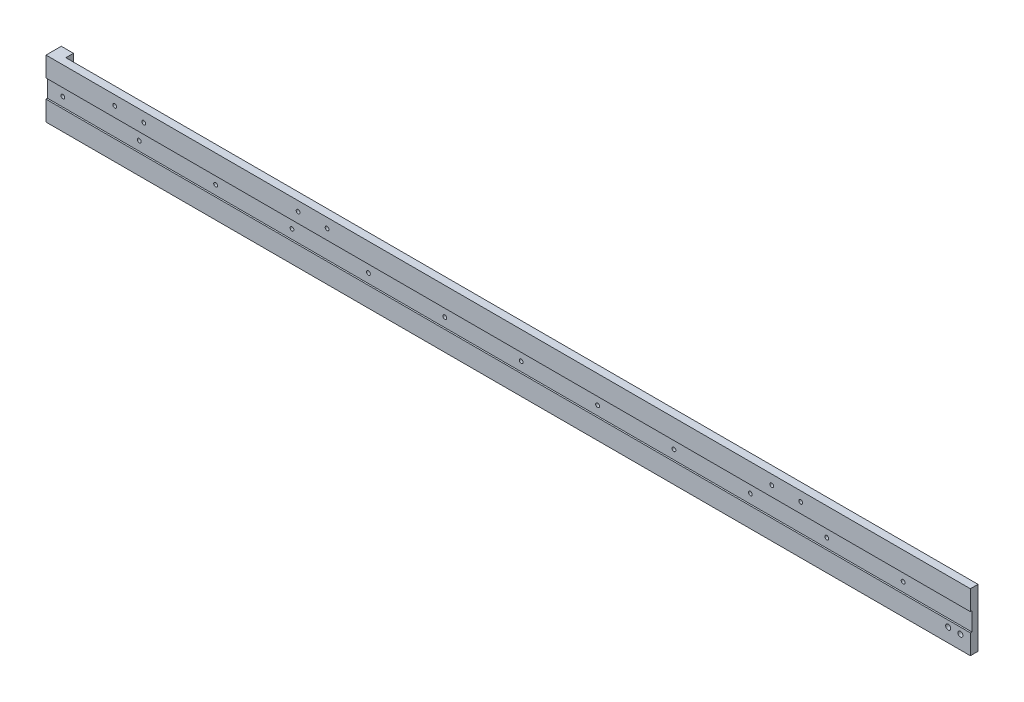
SolidWorks part; units mm, degrees
ref_plane "前视基准面" through (0, 0, 0) normal (0, 0, 1) x (1, 0, 0)
ref_plane "上视基准面" through (0, 0, 0) normal (0, 1, 0) x (1, 0, 0)
ref_plane "右视基准面" through (0, 0, 0) normal (1, 0, 0) x (0, 0, -1)
sketch "草图1" plane through (0, 0, 0) normal (0, 0, 1) x (1, 0, 0)
  line L1 (0, 0) -> (595, 0)
  line L2 (0, 0) -> (0, 38)
  line L3 (0, 38) -> (595, 38)
  line L4 (595, 0) -> (595, 38)
  dimension "D1" = 38
  dimension "D2" = 595
extrude "凸台-拉伸1" add sketch "草图1" along normal blind 5
hole_wizard "M3 螺纹孔1" positions "草图2" profile "草图3" tap size "M3" standard "ISO" end condition through all
sketch "草图2" plane through (0, 0, 5) normal (0, 0, 1) x (1, 0, 0)
  line L0 (0, 19) -> (40.9231, 19) construction
  line L1 (0, 38) -> (0, 0) construction
  point P0 (10, 19)
  dimension "D1" = 10
sketch "草图3" plane through (10, 19, 5) normal (1, 0, 0) x (0, -1, 0)
  line L0 (0, 0) -> (0, 5)
  line L1 (0, 5) -> (1.25, 5)
  line L2 (1.25, 5) -> (1.25, 0)
  line L5 (1.25, 0) -> (0, 0)
  line L11 (0, -6.35) -> (0, 107.95) construction
  dimension "通孔螺纹孔钻头直径" = 2.5
  dimension "通孔螺纹孔钻头深度" = 5
cosmetic thread "孔螺蚊线1" parameters "D2"=3
pattern_linear "阵列(线性)1" count 12 spacing 50 along (1, 0, 0) of "M3 螺纹孔1"
sketch "草图4" plane through (0, 0, 5) normal (0, 0, 1) x (1, 0, 0)
  line L0 (0, 19) -> (90.1433, 19) construction
  line L1 (0, 38) -> (0, 0) construction
  line L2 (595, 0) -> (595, 38) construction
  line L3 (0, 25) -> (595, 25)
  line L4 (0, 25) -> (0, 13)
  line L5 (0, 13) -> (595, 13)
  line L6 (595, 25) -> (595, 13)
  dimension "D1" = 12
extrude "切除-拉伸1" cut sketch "草图4" against normal blind 1
sketch "草图5" plane through (0, 0, 0) normal (-1, 0, 0) x (0, 0, 1)
  line L1 (0, 38) -> (-5, 38)
  line L2 (0, 38) -> (0, 0)
  line L3 (0, 0) -> (-5, 0)
  line L4 (-5, 38) -> (-5, 0)
  dimension "D1" = 5
extrude "凸台-拉伸2" add sketch "草图5" against normal blind 8
hole_wizard "M4 螺纹孔1" positions "草图6" profile "草图7" tap size "M4" standard "ISO"
sketch "草图6" plane through (0, 0, 0) normal (-1, 0, 0) x (0, 0, 1)
  point P0 (0.6955, 14)
  point P3 (0.6955, 4)
sketch "草图7" plane through (0, 14, 0.6955) normal (0, 1, 0) x (0, 0, 1)
  line L0 (0, 0) -> (0, 6.9914)
  line L1 (0, 6.9914) -> (1.65, 6)
  line L2 (1.65, 6) -> (1.65, 0)
  line L5 (1.65, 0) -> (0, 0)
  line L10 (0, 6.9914) -> (-1.65, 6) construction
  line L11 (0, -6.35) -> (0, 107.95) construction
  dimension "螺纹孔钻头直径" = 3.3
  dimension "螺纹孔钻头深度" = 6
  dimension "导头角度" = 118
cosmetic thread "孔螺蚊线2" parameters "D1"=6, "D2"=4
cosmetic thread "孔螺蚊线3" parameters "D1"=6, "D2"=4
sketch "草图8" plane through (595, 0, 0) normal (1, 0, 0) x (0, 0, -1)
  line L0 (-5, 0) -> (-5, 13)
  line L1 (-5, 13) -> (-4, 13)
  line L2 (-4, 13) -> (-4, 25)
  line L3 (-4, 25) -> (-5, 25)
  line L4 (-5, 25) -> (-5, 38)
  line L5 (-5, 38) -> (0, 38)
  line L6 (0, 38) -> (0, 0)
  line L7 (0, 0) -> (-5, 0)
extrude "凸台-拉伸3" add sketch "草图8" along normal blind 10
hole_wizard "M4 螺纹孔2" positions "草图9" profile "草图10" tap size "M4" standard "ISO"
sketch "草图9" plane through (0, 0, 5) normal (0, 0, 1) x (1, 0, 0)
  line L0 (0, 0) -> (605, 0) construction
  line L1 (605, 13) -> (605, 0) construction
  point P3 (598.5, 9.0024)
  point P10 (590.5, 9.0024)
  dimension "D1" = 9.0024
  dimension "D2" = 6.5
  dimension "D3" = 8
sketch "草图10" plane through (598.5, 9.0024, 5) normal (1, 0, 0) x (0, -1, 0)
  line L0 (0, 0) -> (0, 11.0914)
  line L1 (0, 11.0914) -> (1.65, 10.1)
  line L2 (1.65, 10.1) -> (1.65, 0)
  line L5 (1.65, 0) -> (0, 0)
  line L10 (0, 11.0914) -> (-1.65, 10.1) construction
  line L11 (0, -6.35) -> (0, 107.95) construction
  dimension "螺纹孔钻头直径" = 3.3
  dimension "螺纹孔钻头深度" = 10.1
  dimension "导头角度" = 118
cosmetic thread "孔螺蚊线4" parameters "D1"=5, "D2"=4
cosmetic thread "孔螺蚊线5" parameters "D1"=5, "D2"=4
hole_wizard "M3 螺纹孔2" positions "草图12" profile "草图13" tap size "M3" standard "ISO"
sketch "草图12" plane through (0, 0, 0) normal (0, 0, -1) x (-1, 0, 0)
  point P0 (-44.9928, 31.7)
  point P3 (-63.9928, 31.7)
sketch "草图13" plane through (44.9928, 31.7, 0) normal (1, 0, 0) x (0, 1, 0)
  line L0 (0, 0) -> (0, 8.2511)
  line L1 (0, 8.2511) -> (1.25, 7.5)
  line L2 (1.25, 7.5) -> (1.25, 0)
  line L5 (1.25, 0) -> (0, 0)
  line L10 (0, 8.2511) -> (-1.25, 7.5) construction
  line L11 (0, -6.35) -> (0, 107.95) construction
  dimension "螺纹孔钻头直径" = 2.5
  dimension "螺纹孔钻头深度" = 7.5
  dimension "导头角度" = 118
cosmetic thread "孔螺蚊线6" parameters "D1"=5, "D2"=3
cosmetic thread "孔螺蚊线7" parameters "D1"=5, "D2"=3
pattern_linear "阵列(线性)2" count 2 spacing 120 along (1, 0, 0) of "M3 螺纹孔2"
pattern_linear "阵列(线性)3" count 2 spacing 430 along (1, 0, 0) of "M3 螺纹孔2"
